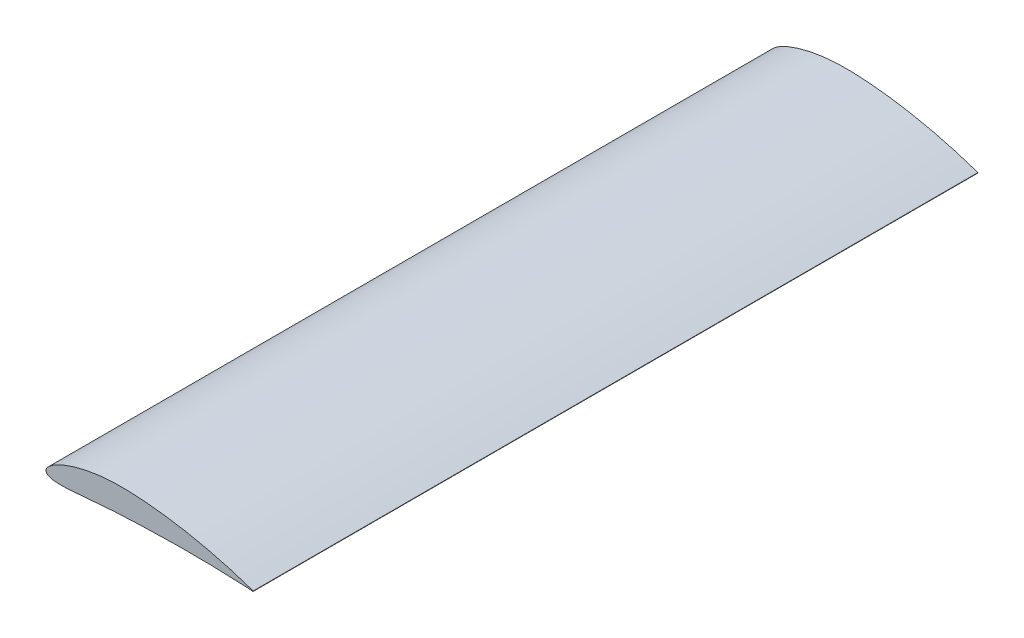
SolidWorks part; units mm, degrees
other "Camera1"
ref_plane "Front Plane" through (0, 0, 0) normal (0, 0, 1) x (1, 0, 0)
ref_plane "Top Plane" through (0, 0, 0) normal (0, 1, 0) x (1, 0, 0)
ref_plane "Right Plane" through (0, 0, 0) normal (1, 0, 0) x (0, 0, -1)
curve "Curve2"
  spline degree 3 poles (1000.25, 1.24, 0) (999.36, 1.5466, 0) (995.8139, 2.7683, 0) (987.8762, 5.5077, 0) (974.7136, 9.9275, 0) (956.465, 15.9446, 0) (933.2861, 23.3123, 0) (905.3935, 31.8009, 0) (873.0611, 41.1442, 0) (836.5996, 51.0483, 0) (796.3762, 61.2143, 0) (752.7953, 71.3209, 0) (706.3231, 81.1144, 0) (657.4446, 90.2776, 0) (606.6871, 98.541, 0) (554.6079, 105.6901, 0) (501.792, 111.4952, 0) (448.8062, 115.7722, 0) (395.8896, 118.5809, 0) (343.6082, 118.9114, 0) (292.6925, 116.357, 0) (244.199, 111.1728, 0) (198.7693, 103.6648, 0) (157.0012, 94.1608, 0) (119.4181, 83.1247, 0) (86.4596, 71.0512, 0) (58.48, 58.4287, 0) (35.7445, 45.7437, 0) (18.354, 33.4445, 0) (6.4016, 21.7983, 0) (-0.4785, 10.7687, 0) (-1.1021, -0.3322, 0) (5.4783, -9.2258, 0) (17.0143, -14.7948, 0) (32.8747, -18.4511, 0) (53.3085, -20.3675, 0) (78.1118, -20.7512, 0) (107.0475, -19.7633, 0) (139.7896, -17.6475, 0) (176.0022, -14.654, 0) (215.3329, -11.125, 0) (257.4273, -7.3624, 0) (301.9209, -3.6922, 0) (348.4441, -0.4557, 0) (396.9816, 1.9832, 0) (447.1013, 3.7059, 0) (498.2783, 5.4818, 0) (549.6221, 6.9005, 0) (600.5599, 7.9279, 0) (650.5484, 8.5041, 0) (699.0372, 8.6069, 0) (745.4858, 8.2663, 0) (789.3705, 7.5598, 0) (830.1852, 6.5089, 0) (867.4516, 5.2968, 0) (900.7439, 3.9432, 0) (929.5972, 2.6539, 0) (953.857, 1.2862, 0) (972.6764, 0.624, 0) (987.1696, -1.0584, 0) (994.3521, -0.0144, 0) (999.8798, -2.0481, 0) (999.9716, -0.4847, 0) (1000, 0, 0) knots 0 0 0 0 0.001372 0.005465 0.012235 0.021602 0.033461 0.047671 0.064081 0.082496 0.102719 0.124527 0.147676 0.171913 0.196978 0.222597 0.248497 0.274385 0.300041 0.32569 0.350525 0.37428 0.396711 0.417577 0.436654 0.453744 0.46868 0.481329 0.491631 0.499616 0.505546 0.510185 0.514824 0.520702 0.528516 0.538466 0.550543 0.564643 0.580638 0.598345 0.617584 0.638174 0.659922 0.682632 0.706121 0.730727 0.7557 0.780732 0.805564 0.829932 0.85357 0.876213 0.89761 0.917519 0.935698 0.951943 0.966047 0.97784 0.987174 0.993932 0.998018 0.999386 1 1 1 1
sketch "Sketch1" plane through (0, 0, 0) normal (0, 0, 1) x (1, 0, 0)
  arc A0 (1000.25, 1.24) -> (1000, 0) centre (1000.0422, 0.6367) cw
  spline S0 degree 3 poles (856.9359, -2933.2024) (1505.4694, -162.2574) (1247.2352, -84.0002) (987.8762, 5.5077) (974.7136, 9.9275) (956.465, 15.9446) (933.2861, 23.3123) (905.3935, 31.8009) (873.0611, 41.1442) (836.5996, 51.0483) (796.3762, 61.2143) (752.7953, 71.3209) (706.3231, 81.1144) (657.4446, 90.2776) (606.6871, 98.541) (554.6079, 105.6901) (501.792, 111.4952) (448.8062, 115.7722) (395.8896, 118.5809) (343.6082, 118.9114) (292.6925, 116.357) (244.199, 111.1728) (198.7693, 103.6648) (157.0012, 94.1608) (119.4181, 83.1247) (86.4596, 71.0512) (58.48, 58.4287) (35.7445, 45.7437) (18.354, 33.4445) (6.4016, 21.7983) (-0.4785, 10.7687) (-1.1021, -0.3322) (5.4783, -9.2258) (17.0143, -14.7948) (32.8747, -18.4511) (53.3085, -20.3675) (78.1118, -20.7512) (107.0475, -19.7633) (139.7896, -17.6475) (176.0022, -14.654) (215.3329, -11.125) (257.4273, -7.3624) (301.9209, -3.6922) (348.4441, -0.4557) (396.9816, 1.9832) (447.1013, 3.7059) (498.2783, 5.4818) (549.6221, 6.9005) (600.5599, 7.9279) (650.5484, 8.5041) (699.0372, 8.6069) (745.4858, 8.2663) (789.3705, 7.5598) (830.1852, 6.5089) (867.4516, 5.2968) (900.7439, 3.9432) (929.5972, 2.6539) (953.857, 1.2862) (972.6764, 0.624) (987.1696, -1.0584) (994.3521, -0.0144) (1012.3874, -6.6496) (918.9793, 128.1334) (2840.5265, -2357.9075) knots -0.387528 -0.387528 -0.387528 -0.387528 0.001372 0.005465 0.012235 0.021602 0.033461 0.047671 0.064081 0.082496 0.102719 0.124527 0.147676 0.171913 0.196978 0.222597 0.248497 0.274385 0.300041 0.32569 0.350525 0.37428 0.396711 0.417577 0.436654 0.453744 0.46868 0.481329 0.491631 0.499616 0.505546 0.510185 0.514824 0.520702 0.528516 0.538466 0.550543 0.564643 0.580638 0.598345 0.617584 0.638174 0.659922 0.682632 0.706121 0.730727 0.7557 0.780732 0.805564 0.829932 0.85357 0.876213 0.89761 0.917519 0.935698 0.951943 0.966047 0.97784 0.987174 0.993932 0.998018 0.999386 1.013731 1.013731 1.013731 1.013731 only from (1000.25, 1.24) to (1000, 0) construction
  spline S1 degree 3 poles (1000.25, 1.24) (999.36, 1.5466) (995.8139, 2.7683) (987.8762, 5.5077) (974.7136, 9.9275) (956.465, 15.9446) (933.2861, 23.3123) (905.3935, 31.8009) (873.0611, 41.1442) (836.5996, 51.0483) (796.3762, 61.2143) (752.7953, 71.3209) (706.3231, 81.1144) (657.4446, 90.2776) (606.6871, 98.541) (554.6079, 105.6901) (501.792, 111.4952) (448.8062, 115.7722) (395.8896, 118.5809) (343.6082, 118.9114) (292.6925, 116.357) (244.199, 111.1728) (198.7693, 103.6648) (157.0012, 94.1608) (119.4181, 83.1247) (86.4596, 71.0512) (58.48, 58.4287) (35.7445, 45.7437) (18.354, 33.4445) (6.4016, 21.7983) (-0.4785, 10.7687) (-1.1021, -0.3322) (5.4783, -9.2258) (17.0143, -14.7948) (32.8747, -18.4511) (53.3085, -20.3675) (78.1118, -20.7512) (107.0475, -19.7633) (139.7896, -17.6475) (176.0022, -14.654) (215.3329, -11.125) (257.4273, -7.3624) (301.9209, -3.6922) (348.4441, -0.4557) (396.9816, 1.9832) (447.1013, 3.7059) (498.2783, 5.4818) (549.6221, 6.9005) (600.5599, 7.9279) (650.5484, 8.5041) (699.0372, 8.6069) (745.4858, 8.2663) (789.3705, 7.5598) (830.1852, 6.5089) (867.4516, 5.2968) (900.7439, 3.9432) (929.5972, 2.6539) (953.857, 1.2862) (972.6764, 0.624) (987.1696, -1.0584) (994.3521, -0.0144) (999.8798, -2.0481) (999.9716, -0.4847) (1000, 0) knots 0 0 0 0 0.001372 0.005465 0.012235 0.021602 0.033461 0.047671 0.064081 0.082496 0.102719 0.124527 0.147676 0.171913 0.196978 0.222597 0.248497 0.274385 0.300041 0.32569 0.350525 0.37428 0.396711 0.417577 0.436654 0.453744 0.46868 0.481329 0.491631 0.499616 0.505546 0.510185 0.514824 0.520702 0.528516 0.538466 0.550543 0.564643 0.580638 0.598345 0.617584 0.638174 0.659922 0.682632 0.706121 0.730727 0.7557 0.780732 0.805564 0.829932 0.85357 0.876213 0.89761 0.917519 0.935698 0.951943 0.966047 0.97784 0.987174 0.993932 0.998018 0.999386 1 1 1 1
extrude "Boss-Extrude1" add sketch "Sketch1" along normal blind 7000 contours S1 A0
scale "Scale1" bodies to scale 101 scale about origin uniform scaling no x scale factor 2 y scale factor 2 z scale factor 1
ref_axis "Axis1" through (2000.5, 2.48, 7000) along (0, 0, -1)
ref_plane "Plane1" through (2000.5, 0, 0) normal (1, 0, 0) x (0, 0, -1)
sketch "Sketch2" plane through (0, 0, 7000) normal (0, 0, 1) x (1, 0, 0)
  line L0 (0, 0) -> (2000.5, 2.48)
ref_axis "Axis2" through (-4598.815, -5.7011, 7000) along (1, 0.0012, 0)
ref_point "Point1"
ref_plane "Plane2" through (0, 0, 7000) normal (0, 0, -1) x (1, 0.0012, 0)
ref_plane "Plane4" through (0, 0, 6000) normal (0, 0, -1) x (1, 0.0012, 0)
ref_axis "Axis3" through (2101.5387, 0, 6000) along (-1, 0, 0)
ref_point "Point2"
ref_plane "Plane5" through (0, 0, 1000) normal (0, 0, -1) x (1, 0.0012, 0)
ref_axis "Axis4" through (2101.5387, 0, 1000) along (-1, 0, 0)
ref_point "Point3"
ref_plane "Plane6" through (1600.5, 0, 0) normal (1, 0, 0) x (0, 0, -1)
ref_point "Point4"
ref_point "Point5"
